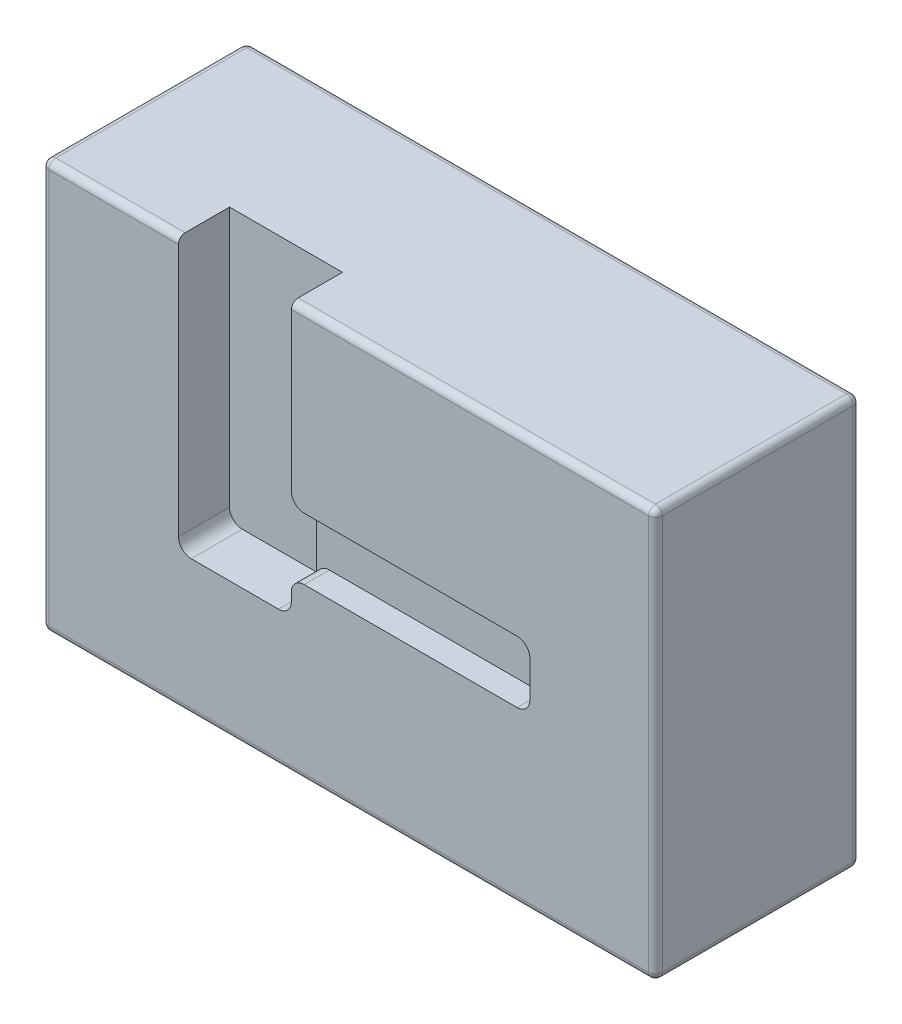
SolidWorks part; units mm, degrees
ref_plane "Alzado" through (0, 0, 0) normal (0, 0, 1) x (1, 0, 0)
ref_plane "Planta" through (0, 0, 0) normal (0, 1, 0) x (1, 0, 0)
ref_plane "Vista lateral" through (0, 0, 0) normal (1, 0, 0) x (0, 0, -1)
sketch "Croquis1" plane through (0, 0, 0) normal (0, 0, 1) x (1, 0, 0)
  line L0 (0, 0) -> (0, 152.4)
  line L1 (0, 152.4) -> (143.7, 152.4)
  line L2 (143.7, 152.4) -> (143.7, 137.35)
  line L3 (143.7, 137.35) -> (228.6, 137.35)
  line L4 (228.6, 137.35) -> (228.6, 0)
  line L5 (228.6, 0) -> (0, 0)
  line L6 (52.8, 152.4) -> (90.9, 152.4)
  line L7 (90.9, 84.55) -> (90.9, 152.4)
  line L8 (52.8, 52.8) -> (52.8, 152.4)
  line L9 (52.8, 52.8) -> (90.9, 52.8)
  line L10 (90.9, 52.8) -> (90.9, 65.5)
  line L11 (90.9, 65.5) -> (179.8, 65.5)
  line L12 (179.8, 65.5) -> (179.8, 84.55)
  line L13 (179.8, 84.55) -> (90.9, 84.55)
  line L14 (90.9, 84.55) -> (90.9, 65.5)
  line L15 (92.9, 50.8) -> (92.9, 65.5)
  line L16 (50.8, 50.8) -> (92.9, 50.8)
  line L17 (50.8, 50.8) -> (50.8, 154.4)
  line L18 (50.8, 154.4) -> (92.9, 154.4)
  line L19 (92.9, 84.55) -> (92.9, 154.4)
  line L20 (90.9, 63.5) -> (181.8, 63.5)
  line L21 (181.8, 63.5) -> (181.8, 86.55)
  line L22 (181.8, 86.55) -> (90.9, 86.55)
  dimension "D2" = 50.8
  dimension "D3" = 50.8
  dimension "D4" = 152.4
  dimension "D5" = 12.7
  dimension "D6" = 38.1
  dimension "D7" = 50.8
  dimension "D8" = 19.05
  dimension "D9" = 88.9
  dimension "D10" = 50.8
  dimension "D13" = 228.6
  dimension "D11" = 2
  dimension "D12" = 2
extrude "Saliente-Extruir1" add sketch "Croquis1" along normal blind 19.05 contours L13 L12 L11 L10 L9 L8 L1 L0 L5 L4 L3 L2 L7 | L12 L13 L7 L1 L8 L9 L10 L11 | L13 L14 L11 L12 | L20 L10 L9 L8 L1 L17 L16 L15 | L22 L19 L1 L7 | L21 L22 L19 L13 L12 L11 L15 L20 | L10 L20 L15 L11 | L19 L22 L7 L13 region at (2.7474, 76.2, 0) region at (51.8, 151.3002, 0) region at (71.85, 102.6, 0) region at (91.9, 119.475, 0) region at (91.9, 85.55, 0) region at (91.9, 64.5, 0) region at (93.8184, 64.5, 0) region at (135.35, 75.025, 0)
extrude "Saliente-Extruir2" add sketch "Croquis1<4>" along normal blind 38.1 contours L13 L12 L11 L10 L9 L8 L1 L0 L5 L4 L3 L2 L7 region at (2.7474, 76.2, 0)
sketch "Croquis1<4>" plane through (0, 0, 0) normal (0, 0, 1) x (1, 0, 0) same geometry as "Croquis1"
extrude "Saliente-Extruir3" add sketch "Croquis1<5>" along normal blind 28.702 contours L13 L14 L11 L12 | L21 L22 L19 L13 L12 L11 L15 L20 region at (93.8184, 64.5, 0) region at (135.35, 75.025, 0)
sketch "Croquis1<5>" plane through (0, 0, 0) normal (0, 0, 1) x (1, 0, 0) same geometry as "Croquis1"
sketch "Croquis2" plane through (0, 0, 38.1) normal (0, 0, 1) x (1, 0, 0)
  line L1 (92.9, 50.8) -> (50.8, 50.8)
  line L2 (92.9, 50.8) -> (92.9, 152.4)
  line L3 (92.9, 152.4) -> (50.8, 152.4)
  line L4 (50.8, 50.8) -> (50.8, 152.4)
extrude "Cortar-Extruir1" cut sketch "Croquis2" against normal up to surface (19.05 mm away) up to face at (81.875, 88.3125, 19.05)
fillet "Redondeo1" radius 4.7625 6 edges at (181.8, 63.5, 33.401) (181.8, 86.55, 33.401) (92.9, 63.5, 33.401) (92.9, 86.55, 33.401) (92.9, 50.8, 28.575) (50.8, 50.8, 28.575)
sketch "Croquis4" plane through (0, 137.35, 0) normal (0, 1, 0) x (1, 0, 0)
  line L1 (143.7, 0) -> (228.6, 0)
  line L2 (143.7, 0) -> (143.7, -38.1)
  line L3 (143.7, -38.1) -> (228.6, -38.1)
  line L4 (228.6, 0) -> (228.6, -38.1)
extrude "Saliente-Extruir4" add sketch "Croquis4" along normal up to surface (15.05 mm away) up to face at (71.85, 152.4, 23.8125)
sketch "Croquis5" plane through (0, 0, 0) normal (0, 0, -1) x (-1, 0, 0)
  line L1 (0, 0) -> (-228.6, 0)
  line L2 (0, 0) -> (0, 152.4)
  line L3 (0, 152.4) -> (-228.6, 152.4)
  line L4 (-228.6, 0) -> (-228.6, 152.4)
extrude "Saliente-Extruir5" add sketch "Croquis5" along normal blind 38.1
fillet "Redondeo2" radius 2.54 13 edges at (114.3, 152.4, -38.1) (114.3, 0, 38.1) (114.3, 0, -38.1) (0, 76.2, 38.1) (0, 0, 0) (0, 76.2, -38.1) (0, 152.4, 0) (228.6, 76.2, 38.1) (228.6, 152.4, 0) (228.6, 76.2, -38.1) (228.6, 0, 0) (160.75, 152.4, 38.1) (25.4, 152.4, 38.1)
sketch "Croquis6" plane through (0, 0, -38.1) normal (0, 0, -1) x (-1, 0, 0)
  line L0 (-2.54, 152.4) -> (-50.8, 152.4) construction
  line L1 (0, 2.54) -> (0, 149.86) construction
  line L2 (-226.06, 0) -> (-2.54, 0) construction
  line L3 (-228.6, 149.86) -> (-228.6, 2.54) construction
  circle A0 centre (-25.4, 127) radius 10
  circle A1 centre (-203.2, 127) radius 10
  circle A2 centre (-203.2, 25.4) radius 10
  circle A3 centre (-25.4, 25.4) radius 10
  circle A6 centre (-114.3, 25.4) radius 10
  point P14 (0, 0)
  dimension "D1" = 20
  dimension "D2" = 25.4
  dimension "D3" = 25.4
  dimension "D4" = 25.4
  dimension "D5" = 25.4
  dimension "D6" = 114.3
extrude "Cortar-Extruir2" cut sketch "Croquis6" against normal blind 71.2
